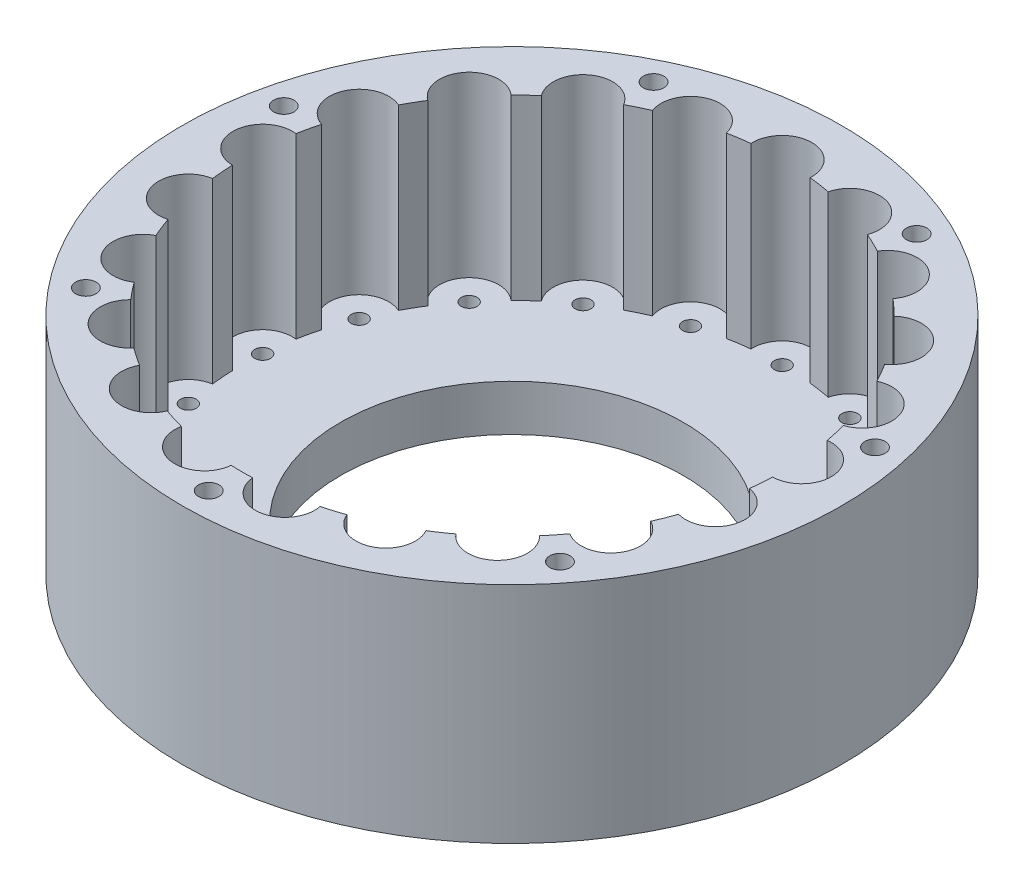
SolidWorks part; units mm, degrees
ref_plane "Ebene vorne" through (0, 0, 0) normal (0, 0, 1) x (1, 0, 0)
ref_plane "Ebene oben" through (0, 0, 0) normal (0, 1, 0) x (1, 0, 0)
ref_plane "Ebene rechts" through (0, 0, 0) normal (1, 0, 0) x (0, 0, -1)
sketch "Skizze1" plane through (0, 0, 0) normal (0, 1, 0) x (1, 0, 0)
  circle A0 centre (0, 0) radius 50
  dimension "D2" = 100
extrude "Aufsatz-Linear austragen1" add sketch "Skizze1" along normal blind 7
sketch "Skizze2" plane through (0, 7, 0) normal (0, 1, 0) x (1, 0, 0)
  circle A0 centre (0, 0) radius 50
  circle A1 centre (0, 0) radius 41
  dimension "D1" = 82
  dimension "D2" = 100
extrude "Aufsatz-Linear austragen2" add sketch "Skizze2" along normal blind 27
sketch "Skizze3" plane through (0, 7, 0) normal (0, 1, 0) x (1, 0, 0)
  circle A0 centre (0, 0) radius 26
  dimension "D1" = 52
extrude "Schnitt-Linear austragen1" cut sketch "Skizze3" against normal blind 27
sketch "Skizze4" plane through (0, 34, 0) normal (0, 1, 0) x (1, 0, 0)
  line L0 (0, 0) -> (0, -50000) construction
  circle A1 centre (0, 41) radius 4.5
  circle A3 centre (0, 0) radius 41 construction
  dimension "D1" = 9
extrude "Schnitt-Linear austragen2" cut sketch "Skizze4" against normal up to surface (27 mm away) up to face at (0, 7, 26)
pattern_circular "Kreismuster1" count 21 over 360 about axis through (0, 7, 0) along (0, 1, 0) of "Schnitt-Linear austragen2"
hole_wizard "Ø2.4 (2.4) Durchmesser Bohrung1" positions "Skizze5" profile "Skizze6" hole size "Ø2.4" standard "ISO" end condition through all
sketch "Skizze5" plane through (0, 7, 0) normal (0, 1, 0) x (1, 0, 0)
  line L0 (0, 0) -> (0, -50000) construction
  point P5 (0, 41)
sketch "Skizze6" plane through (0, 7, -41) normal (1, 0, 0) x (0, 0, 1)
  line L0 (0, 0) -> (0, 7)
  line L1 (0, 7) -> (1.2, 7)
  line L2 (1.2, 7) -> (1.2, 0)
  line L5 (1.2, 0) -> (0, 0)
  line L11 (0, -6.35) -> (0, 107.95) construction
  dimension "Bohrerdurchmesser" = 2.4
  dimension "Bohrungstiefe" = 7
pattern_circular "Kreismuster2" count 21 over 360 about axis through (0, 7, 0) along (0, 1, 0) of "Ø2.4 (2.4) Durchmesser Bohrung1"
hole_wizard "Ø3.1 (3.1) Durchmesser Bohrung1" positions "Skizze7" profile "Skizze8" hole size "Ø3.1" standard "ISO" end condition through all
sketch "Skizze7" plane through (0, 34, 0) normal (0, 1, 0) x (1, 0, 0)
  line L2 (0, 0) -> (0, -50000) construction
  point P10 (0, -46)
  dimension "D1" = 46
sketch "Skizze8" plane through (0, 34, 46) normal (1, 0, 0) x (0, 0, 1)
  line L0 (0, 0) -> (0, 34)
  line L1 (0, 34) -> (1.55, 34)
  line L2 (1.55, 34) -> (1.55, 0)
  line L5 (1.55, 0) -> (0, 0)
  line L11 (0, -6.35) -> (0, 107.95) construction
  dimension "Bohrerdurchmesser" = 3.1
  dimension "Bohrungstiefe" = 34
pattern_circular "Kreismuster3" count 7 over 360 about axis through (0, 7, 0) along (0, 1, 0) of "Ø3.1 (3.1) Durchmesser Bohrung1"
